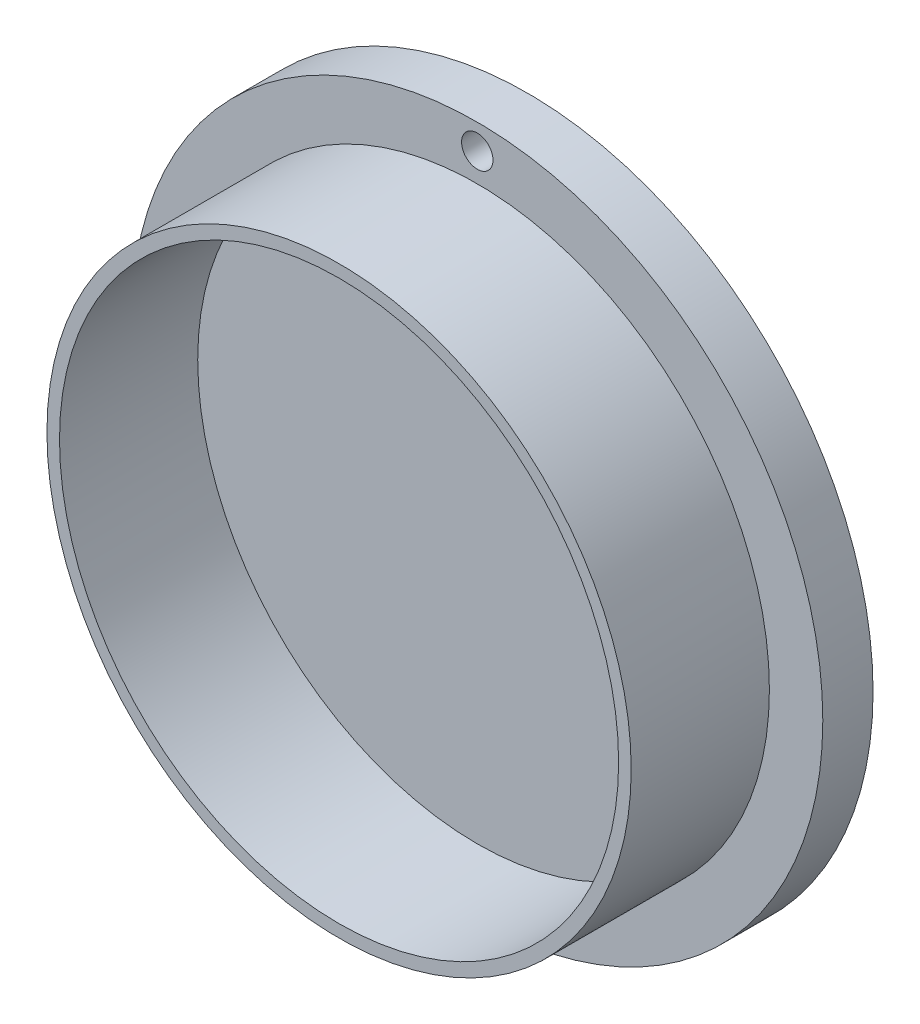
SolidWorks part; units mm, degrees
ref_plane "Front Plane" through (0, 0, 0) normal (0, 0, 1) x (1, 0, 0)
ref_plane "Top Plane" through (0, 0, 0) normal (0, 1, 0) x (1, 0, 0)
ref_plane "Right Plane" through (0, 0, 0) normal (1, 0, 0) x (0, 0, -1)
sketch "Sketch1" plane through (0, 0, 0) normal (0, 0, 1) x (1, 0, 0)
  circle A0 centre (0, 0) radius 55
  circle A1 centre (0, 0) radius 46.5
  point P4 (0, 0)
  dimension "D1" = 110
  dimension "D2" = 93
extrude "Boss-Extrude1" add sketch "Sketch1" along normal blind 30 contours A1 region at (0, 0, 0)
extrude "Boss-Extrude2" add sketch "Sketch1<3>" along normal blind 8 contours A0 A1 region at (-53.4444, 0, 0)
sketch "Sketch1<3>" plane through (0, 0, 0) normal (0, 0, 1) x (1, 0, 0) same geometry as "Sketch1"
sketch "Sketch2" plane through (0, 0, 8) normal (0, 0, 1) x (1, 0, 0)
  circle A0 centre (0, 51) radius 2.5
  circle A1 centre (0, -51) radius 2.5
  point P4 (0, 0)
  point P5 (0, 0)
  point P6 (0, 0)
  dimension "D1" = 5
  dimension "D2" = 5
  dimension "D3" = 102
  dimension "D4" = 51
extrude "Cut-Extrude1" cut sketch "Sketch2" against normal through all and the other way through all
sketch "Sketch3" plane through (0, 0, 30) normal (0, 0, 1) x (1, 0, 0)
  circle A0 centre (0, 0) radius 44.5
  dimension "D1" = 89
extrude "Cut-Extrude2" cut sketch "Sketch3" against normal blind 22
